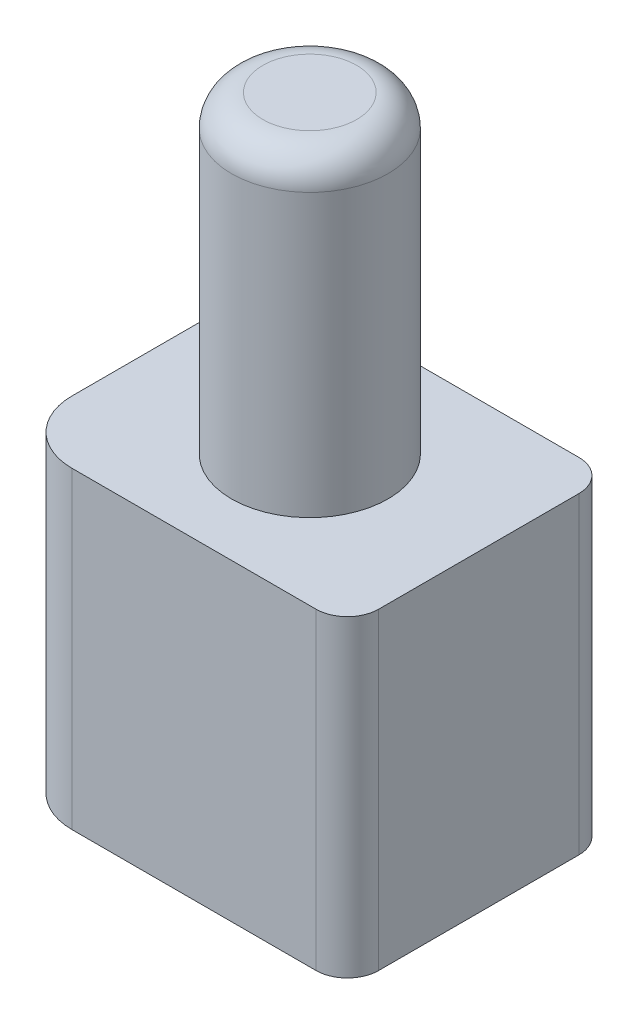
SolidWorks part; units mm, degrees
ref_plane "Front Plane" through (0, 0, 0) normal (0, 0, 1) x (1, 0, 0)
ref_plane "Top Plane" through (0, 0, 0) normal (0, 1, 0) x (1, 0, 0)
ref_plane "Right Plane" through (0, 0, 0) normal (1, 0, 0) x (0, 0, -1)
sketch "Sketch1" plane through (0, 0, 0) normal (0, 1, 0) x (1, 0, 0)
  line L1 (-3.429, 2.667) -> (3.429, 2.667)
  line L2 (-3.429, 2.667) -> (-3.429, -2.667)
  line L3 (-3.429, -2.667) -> (3.429, -2.667)
  line L4 (3.429, 2.667) -> (3.429, -2.667)
  line L5 (-3.429, 2.667) -> (3.429, -2.667) construction
  line L6 (-3.429, -2.667) -> (3.429, 2.667) construction
  point P0 (0, 0)
  dimension "D1" = 6.858
  dimension "D2" = 5.334
extrude "Boss-Extrude1" add sketch "Sketch1" along normal blind 6.35
sketch "Sketch4" plane through (0, 0, 0) normal (0, -1, 0) x (1, 0, 0)
  line L1 (2.159, -0.762) -> (-2.159, -0.762)
  line L2 (2.159, -0.762) -> (2.159, 0.762)
  line L3 (2.159, 0.762) -> (-2.159, 0.762)
  line L4 (-2.159, -0.762) -> (-2.159, 0.762)
  line L5 (2.159, -0.762) -> (-2.159, 0.762) construction
  line L6 (2.159, 0.762) -> (-2.159, -0.762) construction
  line L7 (0.762, 2.159) -> (-0.762, 2.159)
  line L8 (0.762, 2.159) -> (0.762, -2.159)
  line L9 (0.762, -2.159) -> (-0.762, -2.159)
  line L10 (-0.762, 2.159) -> (-0.762, -2.159)
  line L11 (0.762, 2.159) -> (-0.762, -2.159) construction
  line L12 (0.762, -2.159) -> (-0.762, 2.159) construction
  point P0 (0, 0)
  point P6 (0, 0)
  dimension "D1" = 1.524
  dimension "D2" = 1.524
  dimension "D3" = 4.318
  dimension "D4" = 4.318
extrude "Cut-Extrude1" cut sketch "Sketch4" against normal blind 3.556 contours L10 L3 L4 L1 | L3 L10 L1 L8 | L3 L8 L1 L2 | L1 L10 L9 L8 | L7 L10 L3 L8 region at (1.4605, 0, 0) region at (0, 0, -1.4605) region at (0, 0, 0) region at (-1.4605, 0, 0) region at (0, 0, 1.4605)
sketch "Sketch5" plane through (0, 0, 2.159) normal (0, 0, -1) x (-1, 0, 0)
  line L0 (-0.762, 3.556) -> (-0.762, 0) construction
  line L5 (-0.762, 1.778) -> (0.762, 1.778)
  line L6 (-0.762, 1.778) -> (-0.762, 2.921)
  line L7 (-0.762, 2.921) -> (0.762, 2.921)
  line L8 (0.762, 1.778) -> (0.762, 2.921)
  line L9 (-0.762, 1.778) -> (0.762, 2.921) construction
  line L10 (-0.762, 2.921) -> (0.762, 1.778) construction
  line L11 (0.762, 3.556) -> (0.762, 0) construction
  point P4 (0, 2.3495)
  dimension "D1" = 1.143
  dimension "D2" = 1.778
extrude "Boss-Extrude4" add sketch "Sketch5" along normal blind 0.254
fillet "Fillet1" radius 0.127 2 edges at (0, 2.921, 1.905) (0, 1.778, 1.905)
fillet "Fillet3" radius 0.635 3 edges at (-3.429, 3.175, -2.667) (3.429, 3.175, -2.667) (3.429, 3.175, 2.667)
fillet "Fillet4" radius 0.254 12 edges at (-1.4605, 0, 0.762) (-2.159, 0, 0) (-1.4605, 0, -0.762) (-0.762, 0, -1.4605) (0, 0, -2.159) (0.762, 0, -1.4605) (1.4605, 0, -0.762) (2.159, 0, 0) (1.4605, 0, 0.762) (0.762, 0, 1.4605) (0, 0, 2.159) (-0.762, 0, 1.4605)
fillet "Fillet5" radius 0.254 8 edges at (-0.8364, 0.0744, -0.8364) (0.8364, 0.0744, -0.8364) (0.8364, 0.0744, 0.8364) (-0.8364, 0.0744, 0.8364) (-0.762, 1.905, -0.762) (0.762, 1.905, -0.762) (0.762, 1.905, 0.762) (-0.762, 1.905, 0.762)
fillet "Fillet6" radius 1.27 1 edges at (-3.429, 3.175, 2.667)
sketch "Sketch6" plane through (0, 6.35, 0) normal (0, 1, 0) x (1, 0, 0)
  circle A0 centre (0, 0) radius 1.5875
extrude "Boss-Extrude5" add sketch "Sketch6" along normal blind 6.35
fillet "Fillet8" radius 0.635 1 edges at (0, 12.7, 1.5875)
